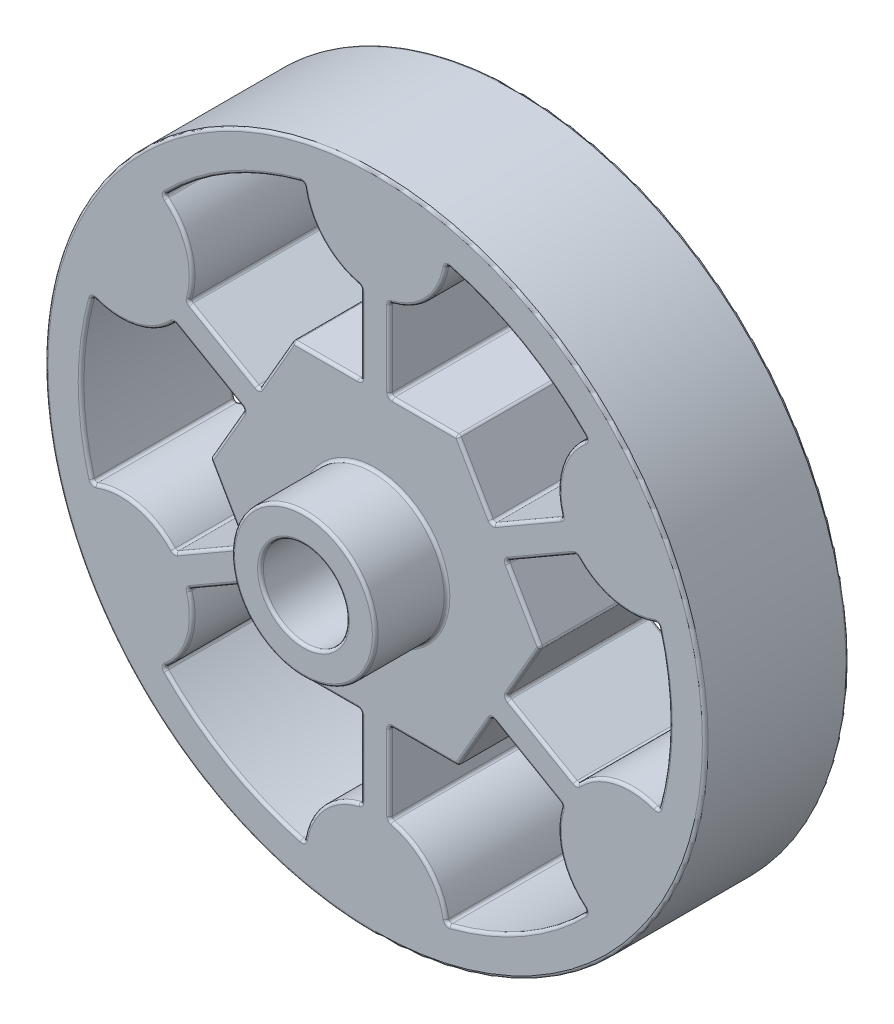
SolidWorks part; units mm, degrees
ref_plane "Front Plane" through (0, 0, 0) normal (0, 0, 1) x (1, 0, 0)
ref_plane "Top Plane" through (0, 0, 0) normal (0, 1, 0) x (1, 0, 0)
ref_plane "Right Plane" through (0, 0, 0) normal (1, 0, 0) x (0, 0, -1)
sketch "Sketch1" plane through (0, 0, 0) normal (0, 0, 1) x (1, 0, 0)
  line L0 (0, 1.5059) -> (0, 50001.5059) construction
  line L1 (11.5, 0) -> (9.125, 4.1136)
  line L2 (5.75, 9.9593) -> (1, 9.9593)
  line L3 (-5.75, 9.9593) -> (-11.5, 0)
  line L4 (-11.5, 0) -> (-9.125, -4.1136)
  line L5 (-5.75, -9.9593) -> (-1, -9.9593)
  line L6 (5.75, -9.9593) -> (8.125, -5.8457)
  line L7 (1, 15.601) -> (1, 9.9593)
  line L8 (-1, 15.601) -> (-1, 9.9593)
  line L9 (14.0109, 6.9345) -> (9.125, 4.1136)
  line L10 (13.0109, 8.6665) -> (8.125, 5.8457)
  line L11 (13.0109, -8.6665) -> (8.125, -5.8457)
  line L12 (14.0109, -6.9345) -> (9.125, -4.1136)
  line L13 (-1, -15.601) -> (-1, -9.9593)
  line L14 (1, -15.601) -> (1, -9.9593)
  line L15 (-14.0109, -6.9345) -> (-9.125, -4.1136)
  line L16 (-13.0109, -8.6665) -> (-8.125, -5.8457)
  line L17 (-13.0109, 8.6665) -> (-8.125, 5.8457)
  line L18 (-14.0109, 6.9345) -> (-9.125, 4.1136)
  line L19 (-1, 9.9593) -> (-5.75, 9.9593)
  line L20 (8.125, 5.8457) -> (5.75, 9.9593)
  line L21 (9.125, -4.1136) -> (11.5, 0)
  line L22 (1, -9.9593) -> (5.75, -9.9593)
  line L23 (-8.125, -5.8457) -> (-5.75, -9.9593)
  circle A0 centre (0, 0) radius 23
  arc A1 (-19.7068, 5.6473) -> (-19.7068, -5.6473) centre (0, 0) ccw
  circle A2 centre (0, 0) radius 9.9593 construction
  arc A3 (-4.9627, 19.8902) -> (-1, 15.601) centre (0, 20.5) ccw
  arc A4 (1, 15.601) -> (4.9627, 19.8902) centre (0, 20.5) ccw
  arc A5 (14.7441, 14.2429) -> (13.0109, 8.6665) centre (17.7535, 10.25) ccw
  arc A6 (14.0109, 6.9345) -> (19.7068, 5.6473) centre (17.7535, 10.25) ccw
  arc A7 (19.7068, -5.6473) -> (14.0109, -6.9345) centre (17.7535, -10.25) ccw
  arc A8 (13.0109, -8.6665) -> (14.7441, -14.2429) centre (17.7535, -10.25) ccw
  arc A9 (4.9627, -19.8902) -> (1, -15.601) centre (0, -20.5) ccw
  arc A10 (-1, -15.601) -> (-4.9627, -19.8902) centre (0, -20.5) ccw
  arc A11 (-14.7441, -14.2429) -> (-13.0109, -8.6665) centre (-17.7535, -10.25) ccw
  arc A12 (-14.0109, -6.9345) -> (-19.7068, -5.6473) centre (-17.7535, -10.25) ccw
  arc A13 (-19.7068, 5.6473) -> (-14.0109, 6.9345) centre (-17.7535, 10.25) ccw
  arc A14 (-13.0109, 8.6665) -> (-14.7441, 14.2429) centre (-17.7535, 10.25) ccw
  arc A15 (-14.7441, -14.2429) -> (-4.9627, -19.8902) centre (0, 0) ccw
  arc A16 (4.9627, -19.8902) -> (14.7441, -14.2429) centre (0, 0) ccw
  arc A17 (19.7068, -5.6473) -> (19.7068, 5.6473) centre (0, 0) ccw
  arc A18 (14.7441, 14.2429) -> (4.9627, 19.8902) centre (0, 0) ccw
  arc A19 (-4.9627, 19.8902) -> (-14.7441, 14.2429) centre (0, 0) ccw
  circle A20 centre (0, 0) radius 5
  circle A21 centre (0, 0) radius 3
  point P44 (0, 0)
  dimension "D1" = 46
  dimension "D2" = 41
  dimension "D4" = 10
  dimension "D7" = 10
  dimension "D8" = 6
  dimension "D3" = 23
  dimension "D5" = 2
  dimension "D6" = 6
extrude "Boss-Extrude1" [suppressed] add sketch "Sketch1" along normal mid plane 10 contours A0 A19 A3 L8 L19 L3 L4 L15 A12 A1 A13 L18 L17 A14 A18 A5 L10 L20 L2 L7 A4 A17 A7 L12 L21 L1 L9 A6 A16 A9 L14 L22 L6 L11 A8 A15 A11 L16 L23 L5 L13 A10
extrude "Boss-Extrude2" add sketch "Sketch1<3>" along normal mid plane 10 contours A0 A20 A19 A3 L8 L19 L3 L4 L15 A12 A1 A13 L18 L17 A14 A18 A5 L10 L20 L2 L7 A4 A17 A7 L12 L21 L1 L9 A6 A16 A9 L14 L22 L6 L11 A8 A15 A11 L16 L23 L5 L13 region at (-22.3495, 0, 0)
sketch "Sketch1<3>" plane through (0, 0, 0) normal (0, 0, 1) x (1, 0, 0) same geometry as "Sketch1"
extrude "Boss-Extrude3" add sketch "Sketch1<4>" along normal mid plane 20 contours A20 A21 region at (-4.8586, 0, 0)
sketch "Sketch1<4>" plane through (0, 0, 0) normal (0, 0, 1) x (1, 0, 0) same geometry as "Sketch1"
fillet "Fillet3" radius 0.2 134 edges at (-14.7441, -14.2429, 0) (-13.0109, -8.6665, 0) (-8.125, -5.8457, 0) (-5.75, -9.9593, 0) (-1, -9.9593, 0) (-1, -15.601, 0) (-4.9627, -19.8902, 0) (4.9627, -19.8902, 0) (1, -15.601, 0) (1, -9.9593, 0) (5.75, -9.9593, 0) (8.125, -5.8457, 0) (13.0109, -8.6665, 0) (14.7441, -14.2429, 0) (19.7068, -5.6473, 0) (14.0109, -6.9345, 0) (9.125, -4.1136, 0) (11.5, 0, 0) (9.125, 4.1136, 0) (14.0109, 6.9345, 0) (19.7068, 5.6473, 0) (14.7441, 14.2429, 0) (13.0109, 8.6665, 0) (8.125, 5.8457, 0) (5.75, 9.9593, 0) (1, 9.9593, 0) (1, 15.601, 0) (4.9627, 19.8902, 0) (-4.9627, 19.8902, 0) (-1, 15.601, 0) (-1, 9.9593, 0) (-5.75, 9.9593, 0) (-8.125, 5.8457, 0) (-13.0109, 8.6665, 0) (-14.7441, 14.2429, 0) (-9.125, 4.1136, 0) (-11.5, 0, 0) (-9.125, -4.1136, 0) (-14.0109, -6.9345, 0) (-19.7068, -5.6473, 0) (-19.7068, 5.6473, 0) (-14.0109, 6.9345, 0) (23, 0, 5) (-3.6726, -17.107, 5) (-1, -12.7802, 5) (-3.375, -9.9593, 5) (-6.9375, -7.9025, 5) (-10.5679, -7.2561, 5) (-12.9788, -11.7341, 5) (-10.25, -17.7535, 5) (12.9788, -11.7341, 5) (10.5679, -7.2561, 5) (6.9375, -7.9025, 5) (3.375, -9.9593, 5) (1, -12.7802, 5) (3.6726, -17.107, 5) (10.25, -17.7535, 5) (16.6514, 5.373, 5) (11.5679, 5.5241, 5) (10.3125, 2.0568, 5) (10.3125, -2.0568, 5) (11.5679, -5.5241, 5) (16.6514, -5.373, 5) (20.5, 0, 5) (3.6726, 17.107, 5) (1, 12.7802, 5) (3.375, 9.9593, 5) (6.9375, 7.9025, 5) (10.5679, 7.2561, 5) (12.9788, 11.7341, 5) (10.25, 17.7535, 5) (-12.9788, 11.7341, 5) (-10.5679, 7.2561, 5) (-6.9375, 7.9025, 5) (-3.375, 9.9593, 5) (-1, 12.7802, 5) (-3.6726, 17.107, 5) (-10.25, 17.7535, 5) (5, 0, 5) (-16.6514, 5.373, 5) (-20.5, 0, 5) (-16.6514, -5.373, 5) (-11.5679, -5.5241, 5) (-10.3125, -2.0568, 5) (-10.3125, 2.0568, 5) (-11.5679, 5.5241, 5) (23, 0, -5) (-3.6726, -17.107, -5) (-1, -12.7802, -5) (-3.375, -9.9593, -5) (-6.9375, -7.9025, -5) (-10.5679, -7.2561, -5) (-12.9788, -11.7341, -5) (-10.25, -17.7535, -5) (12.9788, -11.7341, -5) (10.5679, -7.2561, -5) (6.9375, -7.9025, -5) (3.375, -9.9593, -5) (1, -12.7802, -5) (3.6726, -17.107, -5) (10.25, -17.7535, -5) (16.6514, 5.373, -5) (11.5679, 5.5241, -5) (10.3125, 2.0568, -5) (10.3125, -2.0568, -5) (11.5679, -5.5241, -5) (16.6514, -5.373, -5) (20.5, 0, -5) (3.6726, 17.107, -5) (1, 12.7802, -5) (3.375, 9.9593, -5) (6.9375, 7.9025, -5) (10.5679, 7.2561, -5) (12.9788, 11.7341, -5) (10.25, 17.7535, -5) (-12.9788, 11.7341, -5) (-10.5679, 7.2561, -5) (-6.9375, 7.9025, -5) (-3.375, 9.9593, -5) (-1, 12.7802, -5) (-3.6726, 17.107, -5) (-10.25, 17.7535, -5) (-16.6514, 5.373, -5) (-20.5, 0, -5) (-16.6514, -5.373, -5) (-11.5679, -5.5241, -5) (-10.3125, -2.0568, -5) (-10.3125, 2.0568, -5) (-11.5679, 5.5241, -5) (5, 0, -5) (5, 0, 10) (3, 0, 10) (5, 0, -10) (3, 0, -10)
